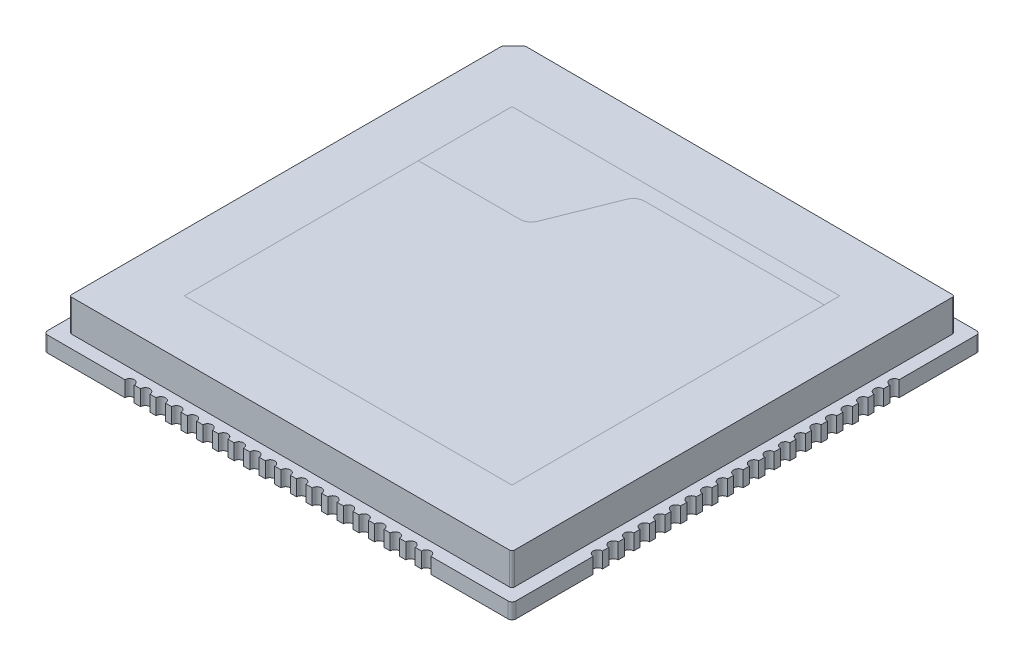
SolidWorks part; units mm, degrees
ref_plane "Спереди" through (0, 0, 0) normal (0, 0, 1) x (1, 0, 0)
ref_plane "Сверху" through (0, 0, 0) normal (0, 1, 0) x (1, 0, 0)
ref_plane "Справа" through (0, 0, 0) normal (1, 0, 0) x (0, 0, -1)
sketch "Эскиз4" plane through (0, 0, 0) normal (0, 1, 0) x (1, 0, 0)
  line L1 (-15, 15) -> (15, 15)
  line L2 (-15, 15) -> (-15, -15)
  line L3 (-15, -15) -> (15, -15)
  line L4 (15, 15) -> (15, -15)
  point P0 (0, 0)
extrude "Бобышка-Вытянуть2" add sketch "Эскиз4" along normal blind 1
fillet "Скругление3" radius 0.25 4 edges at (15, 0.5, -15) (15, 0.5, 15) (-15, 0.5, 15) (-15, 0.5, -15)
sketch "Эскиз18" plane through (0, 1, 0) normal (0, 1, 0) x (1, 0, 0)
  circle A1 centre (-9.5, 15) radius 0.3
extrude "Вырез-Вытянуть1" cut sketch "Эскиз18" against normal through all
pattern_linear "Линейный массив2" count 20 spacing 1 along (1, 0, 0) count 2 spacing 30 along (0, 0, 1) of "Вырез-Вытянуть1"
sketch "Эскиз21" plane through (0, 1, 0) normal (0, 1, 0) x (1, 0, 0)
  line L3 (-15, 14.75) -> (-15, -14.75) construction
  circle A0 centre (-15, -9.5) radius 0.3
extrude "Вырез-Вытянуть2" cut sketch "Эскиз21" against normal through all
pattern_linear "Линейный массив5" count 20 spacing 1 along (0, 0, -1) count 2 spacing 30 along (1, 0, 0) of "Вырез-Вытянуть2"
sketch "Эскиз20" plane through (0, 0, 0) normal (0, -1, 0) x (1, 0, 0)
  line L1 (-15.8, -9.2) -> (-14.2, -9.2)
  line L2 (-15.8, -9.2) -> (-15.8, -9.8)
  line L3 (-15.8, -9.8) -> (-14.2, -9.8)
  line L4 (-14.2, -9.2) -> (-14.2, -9.8)
  point P0 (-9.5, -15)
wrap "Переносить слова23" sketch "Эскиз20" wrap type scribe source sketch "Эскиз20" face at (0, 0, 0)
sketch "Эскиз10" plane through (0, 0, 0) normal (0, -1, 0) x (1, 0, 0)
  circle A1 centre (10.1, -8.6) radius 0.5
wrap "Переносить слова10" sketch "Эскиз10" wrap type scribe source sketch "Эскиз10" face at (-0.1688, 0, -0.1135)
sketch "Эскиз11" plane through (0, 0, 0) normal (0, -1, 0) x (-1, 0, 0)
  circle A0 centre (-10.1, 8.6) radius 1.25
  circle A1 centre (-10.1, 8.6) radius 2.25
wrap "Переносить слова13" sketch "Эскиз11" wrap type scribe source sketch "Эскиз11" face at (10.1, 0, -8.1)
sketch "Эскиз17" [suppressed] plane through (0, 0, 0) normal (0, -1, 0) x (1, 0, 0)
  arc A0 (-9.74, -14.2) -> (-7.34, -14.2) centre (-8.54, -14.2) cw
  arc A1 (-10.84, -14.2) -> (-6.24, -14.2) centre (-8.54, -14.2) cw
  point P0 (-8.54, -14.2)
  point P5 (-8.54, -14.2)
  point P14 (-8.54, -14.2)
sketch "Эскиз5" plane through (0, 1, 0) normal (0, 1, 0) x (1, 0, 0)
  line L1 (-14.18, -14.18) -> (-14.18, 13.5353)
  line L2 (-14.18, 13.5353) -> (-13.43, 14.2853)
  line L3 (-14.18, -14.18) -> (14.18, -14.18)
  line L4 (14.18, 14.18) -> (14.18, -14.18)
  line L6 (-13.43, 14.2853) -> (14.18, 14.18)
  point P0 (0, 0)
extrude "Бобышка-Вытянуть3" add sketch "Эскиз5" along normal blind 2.05
fillet "Скругление4" radius 0.15 5 edges at (-14.18, 2.025, 14.18) (14.18, 2.025, 14.18) (14.18, 2.025, -14.18) (-14.18, 2.025, -13.5353) (-13.43, 2.025, -14.2853)
sketch "Эскиз12" plane through (0, 3.05, 0) normal (0, 1, 0) x (1, 0, 0)
  line L1 (-10.5, 10.5) -> (10.5, 10.5)
  line L2 (-10.5, 10.5) -> (-10.5, -10.5)
  line L3 (-10.5, -10.5) -> (10.5, -10.5)
  line L4 (10.5, 10.5) -> (10.5, -10.5)
  line L5 (-10.5, 10.5) -> (10.5, -10.5) construction
  line L6 (-10.5, -10.5) -> (10.5, 10.5) construction
  point P0 (0, 0)
wrap "Переносить слова14" sketch "Эскиз12" wrap type scribe source sketch "Эскиз12" face at (-2.6931, 3.05, -2.7353)
sketch "Эскиз14" plane through (0, 3.05, 0) normal (0, 1, 0) x (1, 0, 0)
  line L0 (10.5, -10.5) -> (10.5, 10.5) construction
  line L1 (10.5, 10.5) -> (10.5, 9.5)
  line L2 (-4, 4.5) -> (-10.5, 4.5)
  line L3 (10.5, 10.5) -> (-10.5, 10.5)
  line L4 (-10.5, 4.5) -> (-10.5, 10.5)
  line L5 (-1, 9.5) -> (10.5, 9.5)
  line L6 (-3.3143, 4.9642) -> (-1.6857, 9.0358)
  arc A2 (-1.6857, 9.0358) -> (-1, 9.5) centre (-1, 8.7615) cw
  arc A3 (-4, 4.5) -> (-3.3143, 4.9642) centre (-4, 5.2385) ccw
wrap "Переносить слова20" sketch "Эскиз14" wrap type scribe source sketch "Эскиз14" face at (0, 3.05, 0)
